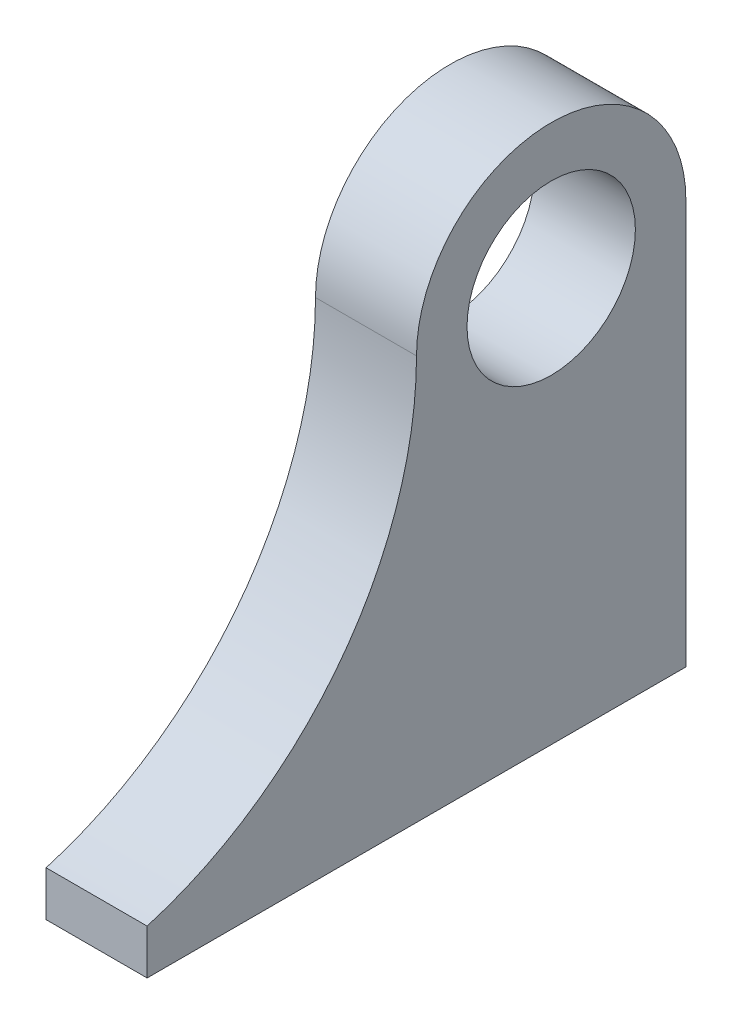
SolidWorks part; units mm, degrees
ref_plane "Alzado" through (0, 0, 0) normal (0, 0, 1) x (1, 0, 0)
ref_plane "Planta" through (0, 0, 0) normal (0, 1, 0) x (1, 0, 0)
ref_plane "Vista lateral" through (0, 0, 0) normal (1, 0, 0) x (0, 0, -1)
sketch "Croquis1" plane through (0, 0, 0) normal (0, 1, 0) x (1, 0, 0)
  line L0 (63.5, 63.5) -> (63.5, 390.652) construction
  line L1 (0, 0) -> (654.05, 0) construction
  line L2 (0, 0) -> (0, 454.152) construction
  line L3 (0, 454.152) -> (654.05, 454.152) construction
  line L4 (654.05, 0) -> (654.05, 454.152) construction
  line L5 (63.5, 390.652) -> (590.55, 390.652) construction
  line L6 (590.55, 63.5) -> (590.55, 390.652) construction
  line L7 (63.5, 63.5) -> (590.55, 63.5) construction
  line L8 (42.3333, 411.8187) -> (611.7167, 411.8187) construction
  line L9 (611.7167, 42.3333) -> (611.7167, 411.8187) construction
  line L10 (42.3333, 42.3333) -> (611.7167, 42.3333) construction
  line L11 (42.3333, 42.3333) -> (42.3333, 411.8187) construction
  line L12 (606.9542, 411.8187) -> (606.9542, 454.152) construction
  line L14 (606.9542, 454.152) -> (602.1917, 454.152)
  line L15 (606.9542, 454.152) -> (606.9542, 411.8187)
  line L16 (606.9542, 411.8187) -> (602.1917, 411.8187)
  line L17 (602.1917, 454.152) -> (602.1917, 411.8187)
  dimension "D1" = 654.05
  dimension "D2" = 454.152
  dimension "D3" = 42.3333
  dimension "D4" = 369.4853
  dimension "D5" = 63.5
  dimension "D6" = 569.3833
  dimension "D7" = 527.05
  dimension "D8" = 327.152
  dimension "D9" = 42.3333
  dimension "D10" = 4.7625
  dimension "D11" = 4.7625
  dimension "D12" = 42.3333
  dimension "D13" = 21.1667
extrude "Saliente-Extruir1" add sketch "Croquis1" along normal blind 25.4
sketch "Croquis2" plane through (606.9542, 0, 0) normal (1, 0, 0) x (0, 0, -1)
  line L0 (432.9853, 25.4) -> (432.9853, 0) construction
  line L1 (411.8187, 25.4) -> (454.152, 25.4) construction
  line L2 (411.8187, 0) -> (454.152, 0) construction
  line L3 (439.3353, 19.05) -> (439.3353, 0)
  line L4 (439.3353, 0) -> (413.9353, 0)
  line L5 (413.9353, 0) -> (411.8187, 0)
  line L6 (413.9353, 0) -> (411.8187, 0) construction
  line L7 (413.9353, 0) -> (413.9353, 2.12)
  line L8 (426.6353, 19.05) -> (432.9853, 19.05) construction
  line L9 (411.8187, 0) -> (411.8187, 25.4)
  line L10 (411.8187, 25.4) -> (454.152, 25.4)
  line L11 (454.152, 25.4) -> (454.152, 0)
  line L12 (454.152, 0) -> (439.3353, 0)
  circle A0 centre (432.9853, 19.05) radius 3.9688
  arc A1 (439.3353, 19.05) -> (426.6353, 19.05) centre (432.9853, 19.05) ccw
  arc A2 (413.9353, 2.12) -> (426.6353, 19.05) centre (409.0009, 19.05) ccw
  point P10 (432.9853, 19.05)
  line M4 (411.8187, 0) -> (454.152, 0)
  line M5 (454.152, 0) -> (454.152, 25.4)
  line M6 (454.152, 25.4) -> (411.8187, 25.4)
  line M7 (411.8187, 25.4) -> (411.8187, 0)
  dimension "D4" = 7.9375
  dimension "D5" = 2.12
  dimension "D3" = 6.35
  dimension "D1" = 25.4
  dimension "D2" = 2.1167
extrude "Cortar-Extruir1" cut sketch "Croquis2" against normal blind 25.4 contours L7 A2 A1 L10 M7 M4 | A1 L3 M4 M5 M6 | A0 region at (606.9542, 12.9536, -446.5453) region at (606.9542, 15.3231, -418.6243) region at (606.9542, 19.05, -432.9853)
